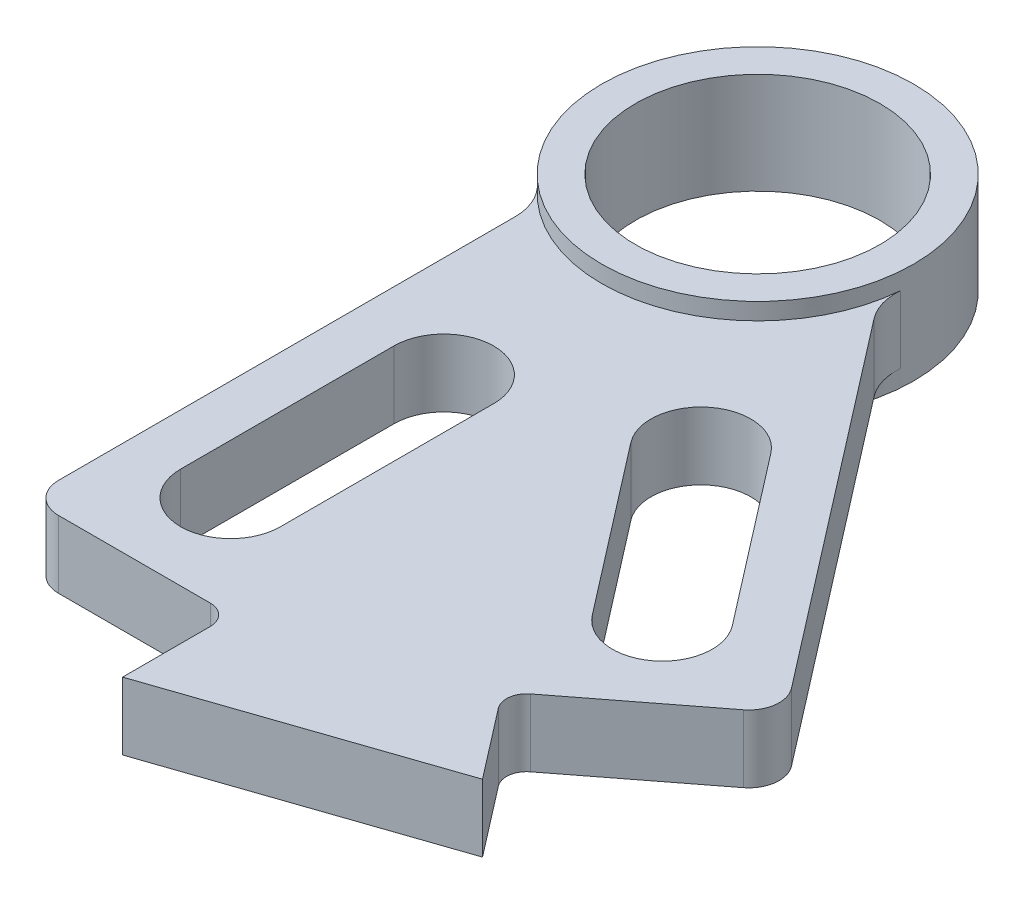
SolidWorks part; units mm, degrees
material "AISI 4130 Steel, normalized at 870C"
ref_plane "Front Plane" through (0, 0, 0) normal (0, 0, 1) x (1, 0, 0)
ref_plane "Top Plane" through (0, 0, 0) normal (0, 1, 0) x (1, 0, 0)
ref_plane "Right Plane" through (0, 0, 0) normal (1, 0, 0) x (0, 0, -1)
sketch "Sketch1" plane through (0, 0, 0) normal (0, 1, 0) x (1, 0, 0)
  line L0 (0, -54.3052) -> (0, -14.6812) construction
  line L1 (33.1712, -42.9969) -> (8.9677, -11.624) construction
  line L2 (0, -49.6062) -> (0, -29.5402) construction
  line L5 (-4.699, -49.6062) -> (-4.699, -29.5402)
  line L8 (-9.525, -59.1312) -> (9.525, -59.1312)
  line L9 (28.5775, -52.636) -> (43.6606, -40.9998)
  line L10 (-9.525, -59.1312) -> (-9.525, -11.1719)
  line L11 (43.6606, -40.9998) -> (14.3657, -3.0274)
  line L12 (9.525, -59.1312) -> (9.525, -69.2912)
  line L13 (28.5775, -52.636) -> (34.7835, -60.6804)
  line L14 (9.525, -69.2912) -> (34.7835, -60.6804)
  line L15 (0, -14.6812) -> (0, 0) construction
  line L16 (0, -59.1312) -> (0, -54.3052) construction
  line L17 (36.119, -46.8179) -> (33.1712, -42.9969)
  line L18 (4.699, -49.6062) -> (4.699, -29.5402)
  line L19 (18.044, -23.3888) -> (30.3009, -39.2764) construction
  line L20 (21.7645, -20.5186) -> (34.0214, -36.4061)
  line L21 (14.3235, -26.2591) -> (26.5804, -42.1466)
  line L22 (8.9677, -11.624) -> (0, 0) construction
  line L23 (0, 0) -> (17.6212, -51.6889) construction
  line L25 (203.1844, -263.3701) -> (17.0665, -22.1219) construction
  line L27 (0, 0) -> (22.1542, -64.9858) construction
  circle A0 centre (0, 0) radius 11.5062
  circle A1 centre (0, 0) radius 14.6812
  arc A2 (-4.699, -49.6062) -> (4.699, -49.6062) centre (0, -49.6062) ccw
  arc A3 (4.699, -29.5402) -> (-4.699, -29.5402) centre (0, -29.5402) ccw
  arc A4 (21.7645, -20.5186) -> (14.3235, -26.2591) centre (18.044, -23.3888) ccw
  arc A5 (26.5804, -42.1466) -> (34.0214, -36.4061) centre (30.3009, -39.2764) ccw
  point P9 (0, -39.5732)
  point P14 (24.1724, -31.3326)
  point P23 (0, -59.1312)
  point P26 (36.119, -46.8179)
  point P33 (0, -54.3052)
  point P36 (33.1712, -42.9969)
  point P38 (0, -24.8412)
  dimension "D2" = 29.3624
  dimension "D3" = 44.45
  dimension "D4" = 4.826
  dimension "D6" = 10.16
  dimension "D5" = 4.826
  dimension "D8" = 10.16
  dimension "D9" = 54.61
  dimension "D7" = 19.05
extrude "Bearing extrude" add sketch "Sketch1" along normal mid plane 9.525 contours A1 A0 region at (-5.9782, 0, -12.9529)
extrude "Boss-Extrude2" add sketch "Sketch1<5>" along normal mid plane 6.35 contours A1 L10 L8 L12 L14 L13 L9 L11 A4 A2 region at (13.1696, 0, 38.6307)
sketch "Sketch1<5>" plane through (0, 0, 0) normal (0, 1, 0) x (1, 0, 0) same geometry as "Sketch1"
sketch3d "Tab Point"
  line L0 (17.6212, 0, 51.6889) -> (17.6212, 22.225, 51.6889) construction
  line L1 (0, 0, 0) -> (17.6212, 0, 51.6889) construction
  line L2 (0, 0, 0) -> (22.1542, 0, 64.9858) construction
  dimension "D1" = 22.225
fillet "Fillet1" radius 5.08 2 edges at (14.3657, 0, 3.0274) (-9.525, 0, 11.1719)
fillet "Fillet2" radius 1.905 2 edges at (28.5775, 0, 52.636) (9.525, 0, 59.1312)
fillet "Fillet3" radius 2.8575 2 edges at (43.6606, 0, 40.9998) (-9.525, 0, 59.1312)
equation "\"Apex_thickness\"= .25"
equation "\"Bearing_diameter\"= .906"
equation "\"A-arm_angle\"= 32.91"
equation "\"D1@Sketch1\"=\"Bearing_diameter\""
equation "\"D1@Boss-Extrude2\"= \"Apex_thickness\""
equation "\"apex slot\"= 1.4"
equation "\"tube diameter\"= 5 / 8"
